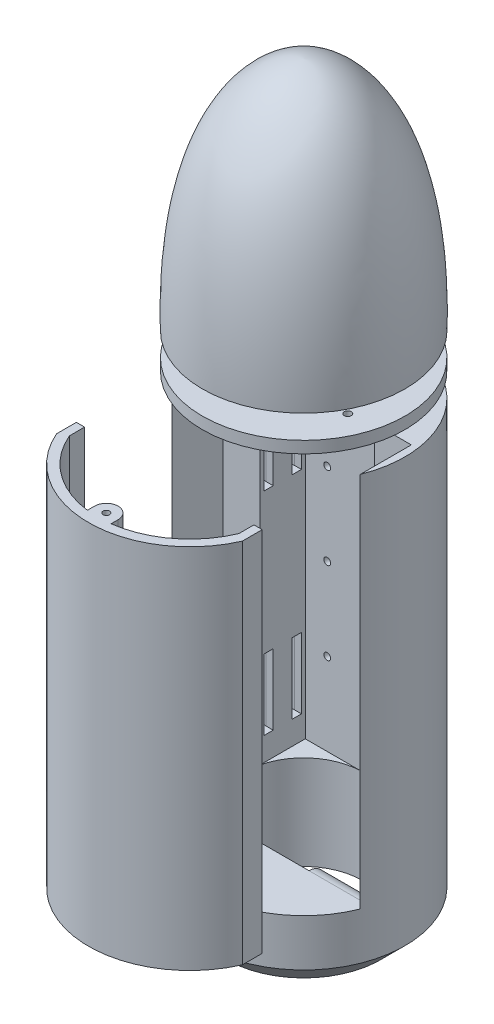
SolidWorks part; units mm, degrees
ref_plane "Front Plane" through (0, 0, 0) normal (0, 0, 1) x (1, 0, 0)
ref_plane "Top Plane" through (0, 0, 0) normal (0, 1, 0) x (1, 0, 0)
ref_plane "Right Plane" through (0, 0, 0) normal (1, 0, 0) x (0, 0, -1)
sketch "Sketch1" plane through (0, 0, 0) normal (0, 1, 0) x (1, 0, 0)
  line L1 (40, -5.75) -> (-40, -5.75)
  line L2 (40, -5.75) -> (40, 5.75)
  line L3 (40, 5.75) -> (-40, 5.75)
  line L4 (-40, -5.75) -> (-40, 5.75)
  line L5 (40, -5.75) -> (-40, 5.75) construction
  line L6 (40, 5.75) -> (-40, -5.75) construction
  circle A0 centre (0, 0) radius 43.0718
  circle A1 centre (0, 0) radius 25
  dimension "D3" = 86.1436
  dimension "D4" = 50
  dimension "D1" = 80
  dimension "D2" = 11.5
extrude "Boss-Extrude1" add sketch "Sketch1" along normal blind 10 contours A0 A1 L3 L2 L1 L4 | L1 A1 region at (0, 0, 13.7788) region at (-41.8536, 0, 0)
sketch "Sketch2" plane through (0, 0, 0) normal (0, -1, 0) x (1, 0, 0)
  circle A0 centre (0, 0) radius 25
  circle A1 centre (0, 0) radius 43.0718
  circle A2 centre (0, 0) radius 22.5
  line M4 (-24.3298, -5.75) -> (-40, -5.75)
  line M5 (-40, -5.75) -> (-40, 5.75)
  arc M7 (24.3298, -5.75) -> (-24.3298, -5.75) centre (0, 0) cw
  line M8 (-40, 5.75) -> (40, 5.75)
  line M9 (40, 5.75) -> (40, -5.75)
  line M10 (40, -5.75) -> (24.3298, -5.75)
  circle M11 centre (0, 0) radius 43.0718
  dimension "D1" = 50
  dimension "D2" = 86.1436
  dimension "D3" = 45
extrude "Boss-Extrude2" add sketch "Sketch2" along normal blind 20 contours A0 M11 M8 M9 M10 M7 M4 M5 | A0 M8 M5 M4 | A0 M10 M9 M8 | A2 M8 region at (-32.3876, 0, 0) region at (32.3876, 0, 0) region at (0, 0, 12.7239) region at (-41.8536, 0, 0)
fillet "Fillet1" radius 7 1 edges at (0, 10, 5.75)
sketch "Sketch3" plane through (0, 10, 0) normal (0, 1, 0) x (1, 0, 0)
  line L0 (-40, -12.75) -> (-40, -15.9744)
  line L1 (40, -12.75) -> (40, -15.9744)
  line L2 (-40, -12.75) -> (-40, 5.75)
  line L3 (-40, 5.75) -> (-24.3298, 5.75)
  line L4 (40, -12.75) -> (40, 5.75)
  line L5 (40, 5.75) -> (24.3298, 5.75)
  circle A0 centre (0, 0) radius 43.0718
  circle A1 centre (0, 0) radius 25
  line M2 (40, 5.75) -> (40, -12.75)
  line M6 (-40, -12.75) -> (-40, 5.75)
  line M7 (-40, 5.75) -> (-24.3298, 5.75)
  arc M8 (-24.3298, 5.75) -> (24.3298, 5.75) centre (0, 0) cw
  line M9 (24.3298, 5.75) -> (40, 5.75)
  circle M10 centre (0, 0) radius 43.0718
  dimension "D1" = 86.1436
  dimension "D2" = 50
extrude "Boss-Extrude3" add sketch "Sketch3" along normal blind 160 contours L1 L0 M2 M10 M6 M7 M8 M9 region at (-40.1044, 10, 14.3622)
ref_plane "Plane1" through (0, 180, 0) normal (0, 1, 0) x (1, 0, 0)
sketch "Sketch18" plane through (0, 170, 0) normal (0, 1, 0) x (1, 0, 0)
  line L1 (-24.3298, 5.75) -> (24.3298, 5.75)
  line L2 (-24.3298, 5.75) -> (-24.3298, 25)
  line L3 (-24.3298, 25) -> (24.3298, 25)
  line L4 (24.3298, 5.75) -> (24.3298, 25)
extrude "Cut-Extrude8" cut sketch "Sketch18" against normal blind 150
sketch "Sketch4" plane through (0, 180, 0) normal (0, 1, 0) x (1, 0, 0)
  line L0 (-24.4949, -5) -> (24.4949, -5)
  circle A0 centre (0, 0) radius 43.0718
  circle A1 centre (0, 0) radius 25
  dimension "D1" = 86.1436
  dimension "D2" = 50
extrude "Boss-Extrude5" add sketch "Sketch4" along normal blind 5 separate body contours A0 A1 | L0 A1 region at (0, 180, 13.3592) region at (-41.8536, 180, 0)
sketch "Sketch6" plane through (0, 10, 0) normal (0, 1, 0) x (1, 0, 0)
  line L1 (-40, -12.75) -> (40, -12.75) construction
  line L2 (40, -12.75) -> (-40, -12.75) construction
  line L3 (0, -12.75) -> (0, -43.0718) construction
  circle A0 centre (-25, -14.75) radius 1.5
  circle A1 centre (0, 0) radius 43.0718 construction
  dimension "D1" = 3
  dimension "D2" = 25
extrude "Cut-Extrude1" cut sketch "Sketch6" against normal blind 10
sketch "Sketch7" plane through (0, 10, 0) normal (0, 1, 0) x (1, 0, 0)
  circle A0 centre (0, -22.1898) radius 5
  dimension "D1" = 10
sketch "Sketch8" plane through (0, 180, 0) normal (0, -1, 0) x (1, 0, 0)
  line L4 (40, 15.9744) -> (40, -5.75)
  line L5 (-40, -5.75) -> (-40, 15.9744)
  line L6 (-24.3298, -5.75) -> (-40, -5.75)
  line L7 (40, -5.75) -> (24.3298, -5.75)
  line L9 (-40, -5.75) -> (-40, 15.9744)
  line L10 (-24.3298, -5.75) -> (-40, -5.75)
  line L11 (40, -5.75) -> (24.3298, -5.75)
  line L15 (-24.3298, -25) -> (-24.3298, -5.75)
  line L16 (-24.3298, -25) -> (-24.3298, -5.75)
  line L17 (24.3298, -25) -> (-24.3298, -25)
  line L18 (24.3298, -25) -> (-24.3298, -25)
  line L19 (24.3298, -5.75) -> (24.3298, -25)
  line L20 (24.3298, -5.75) -> (24.3298, -25)
  line L22 (40, 15.9744) -> (40, -5.75)
  circle A0 centre (30, 11.25) radius 1.5
  circle A1 centre (0, 0) radius 43.0718
  circle A2 centre (0, 0) radius 43.0718
  arc A4 (-40, 15.9744) -> (40, 15.9744) centre (0, 0) ccw
  arc A7 (-40, 15.9744) -> (40, 15.9744) centre (0, 0) ccw
  dimension "D3" = 3
  dimension "D5" = 17
  dimension "D1" = 0
  dimension "D2" = 0
extrude "Cut-Extrude3" cut sketch "Sketch8" against normal through all contours A0 region at (30, 180, 11.25)
sketch "Sketch9" plane through (0, 180, 0) normal (0, -1, 0) x (1, 0, 0)
  line L0 (0, 5) -> (0, 10)
  line L2 (11.5, 10) -> (-11.5, 10)
  line L3 (11.5, 10) -> (11.5, 22)
  line L4 (11.5, 22) -> (-11.5, 22)
  line L5 (-11.5, 10) -> (-11.5, 22)
  line L6 (11.5, 10) -> (-11.5, 22) construction
  line L7 (11.5, 22) -> (-11.5, 10) construction
  line L8 (-24.4949, 5) -> (24.4949, 5) construction
  point P6 (0, 16)
  dimension "D1" = 23
  dimension "D2" = 12
  dimension "D3" = 5
extrude "Cut-Extrude4" cut sketch "Sketch9" against normal through all contours L5 L2 L4 | L3 L4 L2 region at (0, 180, 16)
sketch "Sketch10" plane through (0, 10, 0) normal (0, 1, 0) x (1, 0, 0)
  circle A0 centre (0, -32.0714) radius 1.62
  circle A1 centre (0, 0) radius 43.0718 construction
  dimension "D1" = 3.24
  dimension "D2" = 32.0714
extrude "Cut-Extrude5" cut sketch "Sketch10" against normal blind 5 contours A0
sketch "Sketch12" plane through (0, 0, 0) normal (0, 0, 1) x (1, 0, 0)
  line L0 (0, 195) -> (-43.0718, 195)
  line L1 (0, 195) -> (0, 295)
  line L4 (-38.157, 200) -> (-38.157, 195)
  line L5 (-5, 288.8858) -> (0, 288.8858)
  line L6 (-33.157, 195) -> (-38.157, 200)
  line L7 (-5, 200) -> (-38.157, 200) construction
  line L8 (-5, 200) -> (-5, 288.8858) construction
  line L9 (11.5, 185) -> (-11.5, 185) construction
  line L10 (0, 0) -> (0, 210.2185) construction
  spline S0 degree 3 poles (0, 295) (-18.0651, 293.8361) (-44.9756, 269.8113) (-43.0718, 195) knots 0 0 0 0 1 1 1 1
  spline S1 degree 1 poles (-5, 288.8858) (-38.157, 200) knots 0 0 1 1 construction
  spline S2 degree 3 poles (-5, 288.8858) (-5.4432, 288.7297) (-6.3059, 288.3967) (-8.1035, 287.5804) (-10.3967, 286.2948) (-13.2147, 284.2814) (-17.0056, 280.923) (-21.7223, 275.3682) (-27.0392, 266.2538) (-30.9162, 256.4083) (-33.5245, 247.0682) (-35.1945, 239.3046) (-36.5391, 230.7561) (-37.3562, 222.9573) (-37.8088, 216.2999) (-38.043, 211.0961) (-38.1465, 206.5762) (-38.1721, 202.8602) (-38.1653, 200.9489) (-38.157, 200) knots 0.117292 0.117292 0.117292 0.117292 0.144176 0.17106 0.224828 0.278595 0.332363 0.439899 0.547434 0.654969 0.708737 0.762505 0.816272 0.87004 0.896924 0.923808 0.950692 0.964133 0.977575 0.977575 0.977575 0.977575
  dimension "D1" = 43.0718
  dimension "D2" = 100
  dimension "D5" = 5
  dimension "D6" = 10
revolve "Revolve1" add sketch "Sketch12" angle 360 about L1 region at (-36.4904, 196.6667, 0) region at (-2.5, 289.975, 0)
sketch "Sketch13" plane through (0, 170, 0) normal (0, 1, 0) x (1, 0, 0)
  line L0 (-36, -57.1336) -> (-36, -63.5693)
  line L1 (-40, -57.1336) -> (40, -57.1336)
  line L2 (-40, -15.9744) -> (-40, -64.358)
  line L3 (40, -15.9744) -> (40, -64.358)
  line L4 (36, -57.1336) -> (36, -63.5693)
  line L5 (40, -19.6541) -> (40, -64.358) construction
  line L6 (-36, -19.6541) -> (-36, -63.5693) construction
  line L7 (36, -19.6541) -> (36, -63.5693) construction
  line L8 (-40, -19.6541) -> (-40, -64.358) construction
  line L9 (-36, -63.5693) -> (36, -63.5693)
  line L10 (-39.5, -57.1336) -> (-39.5, -65.5571)
  line L11 (39.5, -57.1336) -> (39.5, -65.5571)
  arc A0 (-40, -64.358) -> (40, -64.358) centre (0, -48.3836) ccw
  arc A1 (-36, -63.5693) -> (36, -63.5693) centre (0, -48.3836) ccw
  arc A2 (40, -15.9744) -> (-40, -15.9744) centre (0, 0) ccw construction
  dimension "D1" = 43.0718
  dimension "D2" = 8.75
  dimension "D4" = 41.1592
  dimension "D5" = 0.5
  dimension "D6" = 0.5
extrude "Boss-Extrude6" add sketch "Sketch13" against normal blind 156 separate body contours A1 L0 L1 L2 A0 L3 L4 region at (-36.8613, 170, 60.3514)
ref_plane "Plane3" through (0, 160, 0) normal (0, 1, 0) x (1, 0, 0)
sketch "Sketch15" plane through (0, 160, 0) normal (0, 1, 0) x (1, 0, 0)
  line L0 (-4.7875, -84.1061) -> (-4.7875, -87.161)
  line L3 (5.2125, -84.1061) -> (-4.7875, -84.1061)
  line L5 (5.2125, -84.1061) -> (5.2125, -87.1061)
  line L10 (-36, -63.5693) -> (-36, -57.1336)
  line L11 (-36, -57.1336) -> (-39.5, -57.1336)
  line L12 (-39.5, -57.1336) -> (-39.5, -65.5571)
  line L13 (39.5, -65.5571) -> (39.5, -57.1336)
  line L14 (39.5, -57.1336) -> (36, -57.1336)
  line L15 (36, -57.1336) -> (36, -63.5693)
  line L16 (-36, -63.5693) -> (-36, -57.1336)
  line L17 (-36, -57.1336) -> (-39.5, -57.1336)
  line L18 (-39.5, -57.1336) -> (-39.5, -65.5571)
  line L19 (39.5, -65.5571) -> (39.5, -57.1336)
  line L20 (39.5, -57.1336) -> (36, -57.1336)
  line L21 (36, -57.1336) -> (36, -63.5693)
  circle A2 centre (0.2125, -84.1061) radius 5
  circle A3 centre (0.2125, -84.1061) radius 1.37
  arc A6 (-36, -63.5693) -> (36, -63.5693) centre (0, -48.3836) ccw
  arc A7 (-39.5, -65.5571) -> (39.5, -65.5571) centre (0, -48.3836) ccw
  arc A8 (-36, -63.5693) -> (36, -63.5693) centre (0, -48.3836) ccw
  arc A9 (-39.5, -65.5571) -> (39.5, -65.5571) centre (0, -48.3836) ccw
  dimension "D3" = 2.74
  dimension "D1" = 3
  dimension "D2" = 10
  dimension "D4" = 0
extrude "Boss-Extrude7" add sketch "Sketch15" along normal up to surface (10 mm away) contours A3 L3 A2 | A3 L3 A2 | A2 | A2 region at (-4.4556, 160, 86.4635) region at (0.2125, 160, 81.859) region at (0.2047, 160, 85.7855) region at (4.8915, 160, 86.4245) up to face at (0, 170, 67.0714)
ref_plane "Plane4" through (0, 110, 0) normal (0, 1, 0) x (1, 0, 0)
sketch "Sketch16" plane through (0, 110, 0) normal (0, 1, 0) x (1, 0, 0)
  line L8 (-36, -63.5693) -> (-36, -57.1336)
  line L9 (-36, -57.1336) -> (-39.5, -57.1336)
  line L10 (-39.5, -57.1336) -> (-39.5, -65.5571)
  line L11 (39.5, -65.5571) -> (39.5, -57.1336)
  line L12 (39.5, -57.1336) -> (36, -57.1336)
  line L13 (36, -57.1336) -> (36, -63.5693)
  line L14 (5.2125, -87.1061) -> (5.2125, -84.1061)
  line L15 (-4.7875, -84.1061) -> (-4.7875, -87.161)
  line L16 (-36, -63.5693) -> (-36, -57.1336)
  line L17 (-36, -57.1336) -> (-39.5, -57.1336)
  line L18 (-39.5, -57.1336) -> (-39.5, -65.5571)
  line L19 (39.5, -65.5571) -> (39.5, -57.1336)
  line L20 (39.5, -57.1336) -> (36, -57.1336)
  line L21 (36, -57.1336) -> (36, -63.5693)
  line L22 (5.2125, -87.1061) -> (5.2125, -84.1061)
  line L23 (-4.7875, -84.1061) -> (-4.7875, -87.161)
  circle A1 centre (0.2125, -84.1061) radius 1.37
  circle A2 centre (0.2125, -84.1061) radius 5
  arc A7 (-36, -63.5693) -> (-4.7875, -87.161) centre (0, -48.3836) ccw
  arc A8 (-39.5, -65.5571) -> (39.5, -65.5571) centre (0, -48.3836) ccw
  arc A9 (5.2125, -87.1061) -> (36, -63.5693) centre (0, -48.3836) ccw
  arc A10 (5.2125, -84.1061) -> (-4.7875, -84.1061) centre (0.2125, -84.1061) ccw
  arc A11 (-36, -63.5693) -> (-4.7875, -87.161) centre (0, -48.3836) ccw
  arc A12 (-39.5, -65.5571) -> (39.5, -65.5571) centre (0, -48.3836) ccw
  arc A13 (5.2125, -87.1061) -> (36, -63.5693) centre (0, -48.3836) ccw
  arc A14 (5.2125, -84.1061) -> (-4.7875, -84.1061) centre (0.2125, -84.1061) ccw
  dimension "D1" = 0
extrude "Boss-Extrude8" add sketch "Sketch16" against normal blind 10 contours A2 A1 | A2 | A2 region at (-24.0788, 110, 80.2406) region at (0.2125, 110, 79.2476)
chamfer "Chamfer1" distance 8.25 angle 45 3 edges at (0.2142, 160, 87.4548) (0.2142, 110, 87.4548) (0.2142, 100, 87.4548)
sketch "Sketch17" plane through (0, 170, 0) normal (0, 1, 0) x (1, 0, 0)
  line L0 (24.3298, 25) -> (-24.3298, 25) construction
  circle A6 centre (-1.2341, 35) radius 3
  dimension "D1" = 10
extrude "Cut-Extrude7" cut sketch "Sketch17" against normal through all and the other way through all contours A6 | A6 region at (-1.2341, 170, -35)
chamfer "Chamfer2" distance 10 distance2 10 1 edges at (0, -20, -43.0718)
sketch "Sketch19" plane through (0, 10, 0) normal (0, 1, 0) x (1, 0, 0)
  line L0 (0, -12.75) -> (0, -1.9529)
  line L1 (-15, -1.9529) -> (15, -1.9529)
  line L2 (-15, -1.9529) -> (-15, -12.75)
  line L3 (-15, -12.75) -> (15, -12.75)
  line L4 (15, -1.9529) -> (15, -12.75)
  line L5 (40, -12.75) -> (-40, -12.75) construction
  line M9 (40, -12.75) -> (-40, -12.75)
  dimension "D1" = 30
extrude "Cut-Extrude9" cut sketch "Sketch19" against normal through all contours L4 L1 L0 M9 | L1 L2 L0 M9 region at (-7.5, 10, 7.3514) region at (7.5, 10, 7.3514)
ref_plane "Plane5" through (0, 150, 0) normal (0, 1, 0) x (1, 0, 0)
sketch "Sketch21" plane through (0, 150, 0) normal (0, 1, 0) x (1, 0, 0)
  line L0 (-24.3298, 5.75) -> (-32.1649, 5.75)
  line L1 (-24.3298, 5.75) -> (-40, 5.75) construction
  line L2 (-24.3298, 5.75) -> (-24.3298, 25)
  line L3 (-24.3298, 15.375) -> (-27.3298, 15.375) construction
  line L4 (-24.3298, 11.375) -> (-27.3298, 11.375)
  line L5 (-24.3298, 19.375) -> (-27.3298, 19.375)
  line L6 (-24.3298, 15.375) -> (-27.3298, 15.375) construction
  line L7 (-24.3298, 7.375) -> (-27.3298, 7.375)
  line L8 (-24.3298, 23.375) -> (-27.3298, 23.375)
  line L9 (0, 0) -> (0, 13.7984) construction
  line L10 (24.3298, 5.75) -> (24.3298, 25)
  line L11 (24.3298, 5.75) -> (32.1649, 5.75)
  line L12 (24.3298, 15.375) -> (27.3298, 15.375) construction
  line L13 (24.3298, 7.375) -> (27.3298, 7.375)
  line L14 (24.3298, 23.375) -> (27.3298, 23.375)
  line L15 (24.3298, 15.375) -> (27.3298, 15.375) construction
  line L16 (24.3298, 11.375) -> (27.3298, 11.375)
  line L17 (24.3298, 19.375) -> (27.3298, 19.375)
  arc A0 (-24.3298, 11.375) -> (-24.3298, 19.375) centre (-24.3298, 15.375) ccw
  arc A1 (-27.3298, 19.375) -> (-27.3298, 11.375) centre (-27.3298, 15.375) ccw
  arc A2 (-24.3298, 7.375) -> (-24.3298, 23.375) centre (-24.3298, 15.375) ccw
  arc A3 (-27.3298, 23.375) -> (-27.3298, 7.375) centre (-27.3298, 15.375) ccw
  arc A4 (24.3298, 7.375) -> (24.3298, 23.375) centre (24.3298, 15.375) cw
  arc A5 (27.3298, 23.375) -> (27.3298, 7.375) centre (27.3298, 15.375) cw
  arc A6 (24.3298, 11.375) -> (24.3298, 19.375) centre (24.3298, 15.375) cw
  arc A7 (27.3298, 19.375) -> (27.3298, 11.375) centre (27.3298, 15.375) cw
  point P9 (-25.8298, 15.375)
  point P14 (-25.8298, 15.375)
  point P29 (25.8298, 15.375)
  point P36 (25.8298, 15.375)
  dimension "D1" = 4
  dimension "D2" = 8
  dimension "D3" = 3
extrude "Cut-Extrude12" cut sketch "Sketch21" against normal blind 30 contours L8 A3 L7 L2 L4 A1 L5 | L17 A7 L16 L10 L13 A5 L14 region at (-25.8298, 150, -7.5692) region at (24.5239, 150, -9.375)
ref_plane "Plane6" through (0, 30, 0) normal (0, 1, 0) x (1, 0, 0)
sketch "Sketch22" plane through (0, 30, 0) normal (0, 1, 0) x (1, 0, 0)
  line L0 (-24.3298, 5.75) -> (-43.4484, 5.75)
  line L1 (-24.3298, 5.75) -> (-24.3298, 25)
  line L2 (-24.3298, 15.375) -> (-27.3298, 15.375) construction
  line L3 (-24.3298, 11.375) -> (-27.3298, 11.375)
  line L4 (-24.3298, 19.375) -> (-27.3298, 19.375)
  line L5 (-24.3298, 15.375) -> (-27.3298, 15.375) construction
  line L6 (-24.3298, 7.375) -> (-27.3298, 7.375)
  line L7 (-24.3298, 23.375) -> (-27.3298, 23.375)
  line L8 (0, -13.8762) -> (0, 13.8762) construction
  line L9 (24.3298, 5.75) -> (24.3298, 25)
  line L10 (24.3298, 5.75) -> (43.4484, 5.75)
  line L11 (24.3298, 15.375) -> (27.3298, 15.375) construction
  line L12 (24.3298, 7.375) -> (27.3298, 7.375)
  line L13 (24.3298, 23.375) -> (27.3298, 23.375)
  line L14 (24.3298, 15.375) -> (27.3298, 15.375) construction
  line L15 (24.3298, 11.375) -> (27.3298, 11.375)
  line L16 (24.3298, 19.375) -> (27.3298, 19.375)
  line L17 (-24.3298, 25) -> (21.6505, 25) construction
  line L18 (-24.3298, 22.4011) -> (-24.3298, 25) construction
  arc A0 (-24.3298, 11.375) -> (-24.3298, 19.375) centre (-24.3298, 15.375) ccw
  arc A1 (-27.3298, 19.375) -> (-27.3298, 11.375) centre (-27.3298, 15.375) ccw
  arc A2 (-24.3298, 7.375) -> (-24.3298, 23.375) centre (-24.3298, 15.375) ccw
  arc A3 (-27.3298, 23.375) -> (-27.3298, 7.375) centre (-27.3298, 15.375) ccw
  arc A4 (24.3298, 7.375) -> (24.3298, 23.375) centre (24.3298, 15.375) cw
  arc A5 (27.3298, 23.375) -> (27.3298, 7.375) centre (27.3298, 15.375) cw
  arc A6 (24.3298, 11.375) -> (24.3298, 19.375) centre (24.3298, 15.375) cw
  arc A7 (27.3298, 19.375) -> (27.3298, 11.375) centre (27.3298, 15.375) cw
  point P5 (-25.8298, 15.375)
  point P10 (-25.8298, 15.375)
  point P24 (25.8298, 15.375)
  point P31 (25.8298, 15.375)
  point P37 (0, 0)
  dimension "D1" = 4
  dimension "D2" = 8
  dimension "D3" = 3
extrude "Cut-Extrude13" cut sketch "Sketch22" along normal blind 30 contours L16 A7 L15 L9 L12 A5 L13 | L7 A3 L6 L1 L3 A1 L4 region at (-25.8298, 30, -7.5692) region at (24.5239, 30, -9.375)
sketch "Sketch24" plane through (0, 0, -25) normal (0, 0, 1) x (1, 0, 0)
  line L0 (0, 190) -> (0, 26.5986) construction
  line L4 (-24.3298, 20) -> (0, 20)
  line L5 (24.3298, 20) -> (24.3298, 170)
  line L6 (24.3298, 170) -> (-24.3298, 170)
  line L7 (-24.3298, 170) -> (-24.3298, 20)
  line L9 (24.3298, 20) -> (24.3298, 170)
  line L10 (24.3298, 170) -> (-24.3298, 170)
  line L11 (-24.3298, 170) -> (-24.3298, 20)
  line L14 (-24.3298, 20) -> (0, 20)
  line L15 (0, 20) -> (24.3298, 20)
  line L16 (0, 20) -> (24.3298, 20)
  circle A0 centre (-15, 160) radius 1.45
  circle A1 centre (15, 160) radius 1.45
  circle A2 centre (15, 125) radius 1.45
  circle A3 centre (15, 90) radius 1.45
  circle A4 centre (15, 55) radius 1.45
  circle A5 centre (-15, 125) radius 1.45
  circle A6 centre (-15, 90) radius 1.45
  circle A7 centre (-15, 55) radius 1.45
  dimension "D1" = 2.9
  dimension "D3" = 10
  dimension "D4" = 15
  dimension "D5" = 2
  dimension "D6" = 4
extrude "Cut-Extrude14" cut sketch "Sketch24" against normal blind 7 contours A1 | A0 | A5 | A2 | A6 | A3 | A4 | A7 region at (-15, 160, -25) region at (15, 160, -25) region at (15, 125, -25) region at (15, 90, -25) region at (15, 55, -25) region at (-15, 125, -25) region at (-15, 90, -25) region at (-15, 55, -25)
sketch "Sketch25" plane through (0, 0, -25) normal (0, 0, 1) x (1, 0, 0)
  line L0 (-15, 160) -> (15, 160)
  line L1 (15, 160) -> (15, 125)
equation "\"PhoneWidth\"= 80"
equation "\"PhoneThickness\"= 11.5"
equation "\"OuterDiam\"= ( sqr ( ( \"PhoneWidth\" / 2 ) ^ 2 + ( \"PhoneThickness\" / 2 ) ) + 3 ) * 2"
equation "\"TubeInnerDia\"= 45'Inner tube Diamiter"
equation "\"TubeOuterDia\"= 50'Outer tube dimiter"
equation "\"TubeLength\"= 300'Total length of tube"
equation "\"PhoneHeight\"=150"
equation "\"ServoLength\"= 23"
equation "\"ServoThickness\"= 12"
equation "\"WireDiamiter\"= 2.24"
equation "\"D3@Sketch1\"=\"OuterDiam\""
equation "\"D1@Sketch12\"=\"OuterDiam\"/2"
equation "\"D1@Sketch1\"=\"PhoneWidth\""
equation "\"D2@Sketch1\"=\"PhoneThickness\""
equation "\"D4@Sketch1\"=\"TubeOuterDia\""
equation "\"D3@Sketch2\"=\"TubeInnerDia\""
equation "\"D1@Sketch2\"=\"TubeOuterDia\""
equation "\"D2@Sketch2\"=\"OuterDiam\""
equation "\"D1@Boss-Extrude3\"=\"PhoneHeight\"+10"
equation "\"D2@Sketch4\"=\"TubeOuterDia\""
equation "\"D1@Sketch4\"=\"OuterDiam\""
equation "\"D2@Sketch12\"=\"PhoneHeight\"/1.5"
equation "\"D1@Sketch13\"=\"OuterDiam\"/2"
equation "\"D2@Sketch13\"=(\"PhoneThickness\"/2) + 3"
equation "\"D1@Boss-Extrude6\"=\"PhoneHeight\"+6"
equation "\"Clearence\"= 0.5"
equation "\"D5@Sketch13\"=\"Clearence\""
equation "\"D6@Sketch13\"=\"Clearence\""
equation "\"D2@Sketch6\"=(\"PhoneWidth\"/2)-15"
equation "\"D1@Sketch3\"=\"OuterDiam\""
equation "\"mountingHoleDiameter\"= 2.9"
equation "\"D1@Sketch24\"=\"mountingHoleDiameter\""
equation "\"D1@Cut-Extrude8\"=\"PhoneHeight\""
